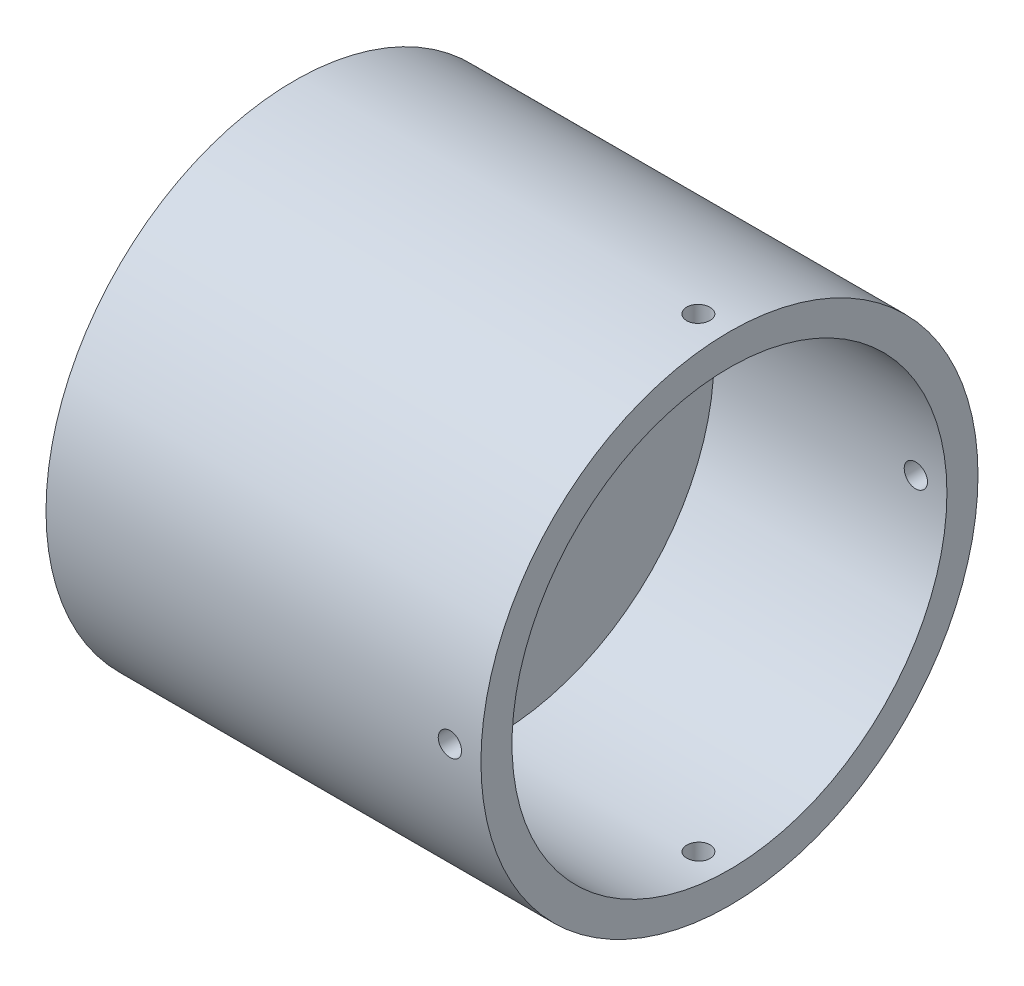
SolidWorks part; units mm, degrees
ref_plane "Plane1" through (0, 0, 0) normal (0, 0, 1) x (1, 0, 0)
ref_plane "Plane2" through (0, 0, 0) normal (0, 1, 0) x (1, 0, 0)
ref_plane "Plane3" through (0, 0, 0) normal (1, 0, 0) x (0, 0, -1)
other "Configuration Table"
sketch "HoldingSke" plane through (0, 0, 0) normal (0, 1, 0) x (1, 0, 0)
  line L0 (0, 0) -> (1.1578, -1.1989)
  line L1 (-15, 0) -> (100, 0) construction
  line L2 (0, 0) -> (-2.1039, 2.3779)
  line L3 (0, 0) -> (-11.863, 4.5341)
  line L4 (0, 0) -> (5.9991, 6.2122)
  line L5 (0, 0) -> (-23.7986, -8.8762)
  line L6 (0, 0) -> (-10.5278, -7.1032)
  line L7 (-2.1039, 2.3779) -> (3.3635, 27.1825)
  line L8 (-76.2, 2.9779) -> (-54.61, 2.9779)
  line L9 (-71.009, 38.7566) -> (-53.1078, 45.2721)
  line L10 (-76.2, 71.12) -> (104.1128, 71.12)
  line L11 (0, 0) -> (-9, 0)
  line L12 (-76.2, 101.6) -> (-76.177, 101.6)
  line L13 (24.9733, 27.94) -> (52.9518, 28.4284)
  line L14 (24.9733, 27.94) -> (24.9743, 27.94)
  line L15 (24.9733, 27.94) -> (100.4006, 29.5858)
  circle A0 centre (0, 0) radius 16
  circle A1 centre (0, 0) radius 12.7
  circle A2 centre (0, 0) radius 12.7
  dimension "Num_teeth" = 46
  dimension "Pitch_radius" = 180.3128
  dimension "Width" = 9
  dimension "Diameter" = 32
sketch "BasProSke" plane through (0, 0, 0) normal (0, 1, 0) x (1, 0, 0)
  line L0 (-10, 0) -> (60, 0) construction
  line L1 (0, 13.2) -> (0, 16)
  line L2 (0, 13.2) -> (9, 13.2)
  line L3 (9, 13.2) -> (9, 16)
  line L4 (9, 16) -> (0, 16)
  dimension "Thickness" = 9
  dimension "Diameter" = 32
revolve "Base-Revolve" add sketch "BasProSke" angle 360 about L0
sketch "TooCutSke" plane through (0, 0, 0) normal (1, 0, 0) x (0, 0, -1)
  line L3 (0.5286, 13.7899) -> (0.5286, 53.6633) construction
  line L4 (0, 0) -> (0, 59.563) construction
  line L5 (0, 0) -> (-4.6628, 68.1682) construction
  line L6 (-5.9043, 11.2944) -> (36.9581, 14.2263) construction
  circle A0 centre (0, 0) radius 13.8 construction
  circle A1 centre (0, 0) radius 14.551 construction
  circle A2 centre (0, 0) radius 11.671 construction
  circle A3 centre (0, 0) radius 13.1746 construction
  arc A4 (0.7405, 13.1538) -> (0.1794, 14.5499) centre (-5.9043, 11.2944) ccw
  arc A5 (0.7405, 13.1538) -> (-0.7405, 13.1538) centre (0, 0) ccw
  arc A6 (0.1794, 14.5499) -> (-0.1794, 14.5499) centre (0, 0) ccw
  arc A7 (-0.1794, 14.5499) -> (-0.7405, 13.1538) centre (5.9043, 11.2944) ccw
extrude "ToothCut" cut sketch "TooCutSke" along normal through all
fillet "Breaks" [suppressed] radius 0.06
fillet "RootFillets" [suppressed] radius 0.151
pattern_circular "TeethCuts" count 46 over 360 about axis through (-10, 0, 0) along (1, 0, 0) of "RootFillets", "Breaks", "ToothCut"
sketch "草图1" plane through (9, 0, 0) normal (1, 0, 0) x (0, 0, -1)
  circle A0 centre (0, 0) radius 16
  circle A1 centre (0, 0) radius 14
  circle A2 centre (0, 0) radius 6
  dimension "D1" = 32
  dimension "D2" = 28
  dimension "D3" = 12
extrude "凸台-拉伸1" add sketch "草图1" along normal blind 4 contours A0 | A2
extrude "凸台-拉伸2" add sketch "草图1<3>" along normal blind 15 from surface contours A0 A1 region at (9, 0, 15.5475) starting at face at (13, 0, -16)
sketch "草图1<3>" plane through (9, 0, 0) normal (1, 0, 0) x (0, 0, -1) same geometry as "草图1"
sketch "草图3" plane through (9, 0, 0) normal (-1, 0, 0) x (0, 0, 1)
  line L0 (0, 0) -> (0, 19.8342) construction
  line L1 (-6.8019, 0) -> (16.8048, 0) construction
  line L2 (0, 8.375) -> (0, -8.375) construction
  line L3 (13, 0) -> (13, -26.6632) construction
  line L4 (16, 0) -> (16, -17.2956) construction
  circle A0 centre (0, 8.375) radius 1
  circle A1 centre (0, -8.375) radius 1
  circle A2 centre (13, 0) radius 1
  circle A3 centre (0, 8.375) radius 2.25
  circle A4 centre (0, -8.375) radius 2.25
  circle A5 centre (13, 0) radius 2.25
  circle A6 centre (0, 0) radius 16 construction
  dimension "D1" = 2
  dimension "D2" = 4.5
  dimension "D3" = 16.75
  dimension "D4" = 3
extrude "切除-拉伸1" cut sketch "草图3" against normal through all both and the other way through all contours A0 | A1
extrude "切除-拉伸2" cut sketch "草图3<3>" against normal blind 3 contours A4 A1 | A3 A0 region at (9, 8.375, -2.1864) region at (9, -8.375, -2.1864)
sketch "草图3<3>" plane through (9, 0, 0) normal (-1, 0, 0) x (0, 0, 1) same geometry as "草图3"
sketch "草图4" plane through (0, 0, 0) normal (0, 1, 0) x (1, 0, 0)
  line L0 (28, 0) -> (0, 0) construction
  line L1 (0, 16) -> (0, -16) construction
  circle A0 centre (26, 0) radius 0.75
  dimension "D1" = 1.5
  dimension "D2" = 26
extrude "切除-拉伸3" cut sketch "草图4" against normal through all both and the other way through all
sketch "草图5" plane through (0, 0, 0) normal (0, 0, 1) x (1, 0, 0)
  line L0 (-19.7584, 0) -> (77.7916, 0) construction
  line L1 (0, 16) -> (0, -16) construction
  circle A0 centre (26, 0) radius 0.75
  dimension "D1" = 1.5
  dimension "D2" = 26
extrude "切除-拉伸4" cut sketch "草图5" against normal through all both and the other way through all
equation "' \"Module@HoldingSke\" = 6.35"
equation "' \"Num_teeth@HoldingSke\" = 24"
equation "' \"Ap@HoldingSke\" =  14.5"
equation "' \"Ap@HoldingSke\" = 14.5"
equation "' \"Width@HoldingSke\" = 12"
equation "' \"Diameter@HoldingSke\" = 8 * 25.4"
equation "' \"Show_teeth@HoldingSke\" = 100"
equation "' \"Backlash@HoldingSke\" = 0.009 * 25.4"
equation "' \"Addendum_fac@HoldingSke\" = 1.0"
equation "' \"Dedendum_fac@HoldingSke\" = 1.25"
equation "' \"Dedendum_add@HoldingSke\" = 0.00005 * 25.4"
equation "' \"Clearance_fac@HoldingSke\" = 0.25"
equation "\"Pitch@HoldingSke\" = 1 / \"Module@HoldingSke\" "
equation "\"Overcut_dia@TooCutSke\" = (\"Num_teeth@HoldingSke\" - 2 * \"Addendum_fac@HoldingSke\") / \"Pitch@HoldingSke\" - 0.002 * 25.4"
equation "\"Pitch_dia@TooCutSke\" = \"Num_teeth@HoldingSke\" / \"Pitch@HoldingSke\""
equation "\"Base_dia@TooCutSke\" = \"Num_teeth@HoldingSke\" / \"Pitch@HoldingSke\" * cos((\"Ap@HoldingSke\"  * 3.14159265 / 180)) * 0.90"
equation "\"Root_dia@TooCutSke\" = \"Num_teeth@HoldingSke\"  / \"Pitch@HoldingSke\" + 2 *  \"Dedendum_fac@HoldingSke\"/ \"Pitch@HoldingSke\" + \"Dedendum_add@HoldingSke\" * 2"
equation "\"Half_ang@TooCutSke\" = 180 / \"Num_teeth@HoldingSke\""
equation "\"Half_CT@TooCutSke\" = \"Num_teeth@HoldingSke\" / \"Pitch@HoldingSke\" * sin((3.14159265 / 2 / \"Num_teeth@HoldingSke\")) / 2 + 10 * \"Backlash@HoldingSke\" / 4"
equation "\"Flank_rad@TooCutSke\" = \"Num_teeth@HoldingSke\" / \"Pitch@HoldingSke\" / 4"
equation "\"Radius@RootFillets\"= \"Clearance_fac@HoldingSke\" / \"Pitch@HoldingSke\" + \"Dedendum_add@HoldingSke\""
equation "\"Break_rad@Breaks\" = 0.02 / \"Pitch@HoldingSke\" * 5"
equation "\"Num_teeth@TeethCuts\" = int( \"Show_teeth@HoldingSke\" ) + 1"
equation "\"Num_teeth@TeethCuts\" = ((sgn( \"Num_teeth@TeethCuts\" - \"Num_teeth@HoldingSke\" )-1)*( \"Num_teeth@TeethCuts\" - \"Num_teeth@HoldingSke\" ))/-2+ \"Num_teeth@HoldingSke\""
equation "\"Num_teeth@TeethCuts\" = ((sgn( \"Num_teeth@TeethCuts\" - 2.0)+1)*( \"Num_teeth@TeethCuts\" - 2.0))/2 +2.0"
equation "\"Angle@TeethCuts\" = 360.0 / \"Num_teeth@HoldingSke\""
equation "\"Diameter@BasProSke\" = \"Num_teeth@HoldingSke\"  / \"Pitch@HoldingSke\" + 2 *  \"Dedendum_fac@HoldingSke\"/ \"Pitch@HoldingSke\" + \"Dedendum_add@HoldingSke\" * 2 + 0.002 * 25.4"
equation "\"Diameter@BasProSke\" = ((sgn( \"Diameter@BasProSke\"  - \"Diameter@HoldingSke\" )+1)*( \"Diameter@BasProSke\"  - \"Diameter@HoldingSke\" ))/2 + \"Diameter@HoldingSke\""
equation "\"Inside_diameter@BasProSke\" =  (\"Num_teeth@HoldingSke\" - 2 * \"Addendum_fac@HoldingSke\") / \"Pitch@HoldingSke\" "
equation "\"Thickness@BasProSke\"  = \"Width@HoldingSke\""
